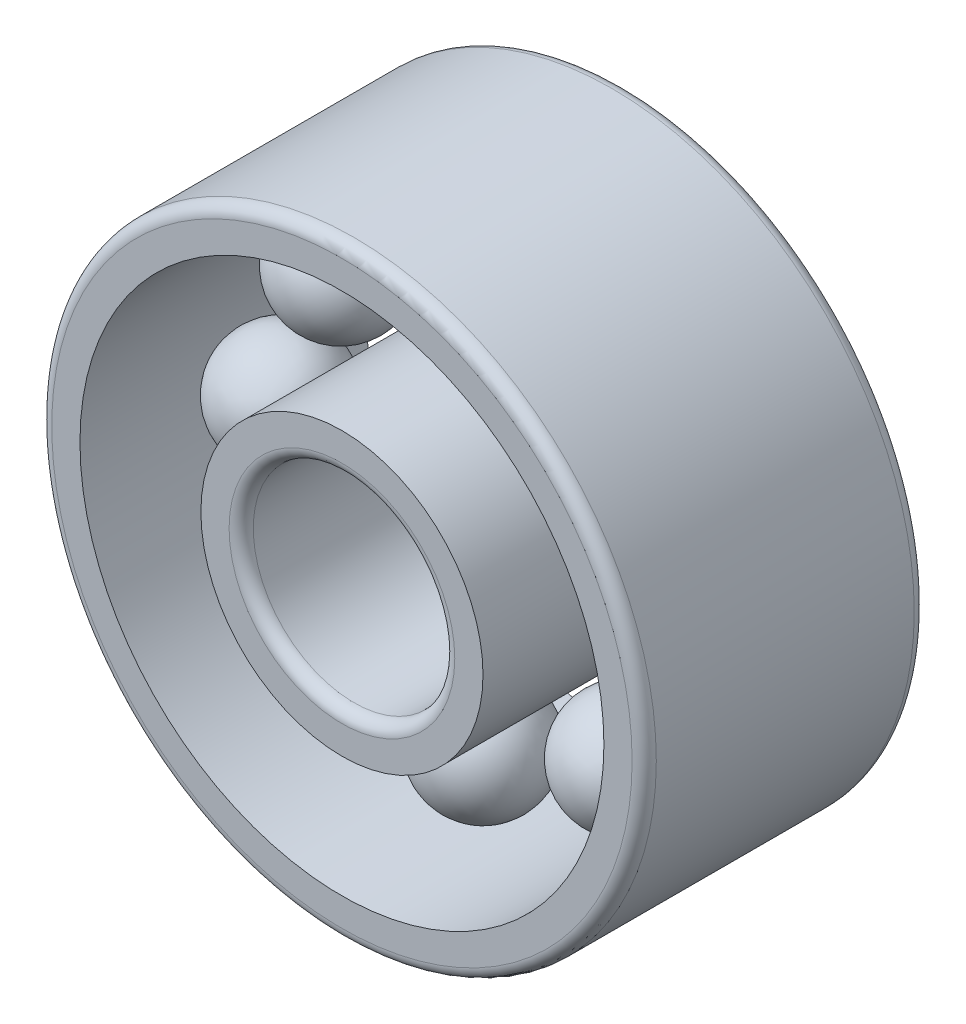
SolidWorks part; units mm, degrees
ref_plane "Front Plane" through (0, 0, 0) normal (0, 0, 1) x (1, 0, 0)
ref_plane "Top Plane" through (0, 0, 0) normal (0, 1, 0) x (1, 0, 0)
ref_plane "Right Plane" through (0, 0, 0) normal (1, 0, 0) x (0, 0, -1)
sketch "S" plane through (0, 0, 0) normal (0, 0, 1) x (1, 0, 0)
  line L0 (-7, 0) -> (7, 0) construction
  circle A0 centre (0, 0) radius 5 construction
  circle A1 centre (0, 0) radius 15 construction
  circle A2 centre (0, 0) radius 7 construction
  circle A3 centre (0, 0) radius 13 construction
  dimension "ID" = 10
  dimension "OD" = 30
  dimension "IDa" = 14
  dimension "ODa" = 26
  dimension "B" = 14
ref_axis "Z" through (0, 0, -7.7) along (0, 0, 1)
sketch "InnerS" plane through (0, 0, 0) normal (0, 1, 0) x (1, 0, 0)
  line L0 (5, -7) -> (7, -7)
  line L1 (7, -7) -> (7, 7)
  line L2 (7, 7) -> (5, 7)
  line L3 (5, 7) -> (5, -7)
  line L4 (0, -11.5) -> (0, 11.5) construction
  dimension "r1" = 5
  dimension "r2" = 7
  dimension "z1" = 7
  dimension "z2" = 7
revolve "InnerRing" add sketch "InnerS" angle 360 about L4
sketch "OuterS" plane through (0, 0, 0) normal (0, 1, 0) x (1, 0, 0)
  line L0 (13, -7) -> (15, -7)
  line L1 (15, -7) -> (15, 7)
  line L2 (15, 7) -> (13, 7)
  line L3 (13, 7) -> (13, -7)
  line L4 (0, -11.5) -> (0, 11.5) construction
  dimension "r1" = 13
  dimension "r2" = 15
  dimension "z1" = 7
  dimension "z2" = 7
revolve "OuterRing" add sketch "OuterS" angle 360 about L4
sketch "BallS" plane through (0, 0, 0) normal (0, 1, 0) x (1, 0, 0)
  line L0 (7.15, 0) -> (12.85, 0)
  arc A0 (7.15, 0) -> (12.85, 0) centre (10, 0) ccw
  dimension "r" = 2.85
  dimension "p" = 10
revolve "Ball" add sketch "BallS" angle 360 about L0
pattern_circular "BallsPattern" count 8 over 360 about axis through (0, 0, -7.7) along (0, 0, 1) of bodies 103
fillet "F1" radius 0.6 2 edges at (15, 0, -7) (15, 0, 7)
fillet "F2" radius 0.6 2 edges at (5, 0, -7) (5, 0, 7)
equation "\"r1@InnerS\" = abs(0.5*\"ID@S\")"
equation "\"r2@InnerS\" = abs(0.5*\"IDa@S\")"
equation "\"z1@InnerS\" = abs(-0.5*\"B@S\")"
equation "\"z2@InnerS\" = abs(0.5*\"B@S\")"
equation "\"r1@OuterS\" = abs(0.5*\"ODa@S\")"
equation "\"r2@OuterS\" = abs(0.5*\"OD@S\")"
equation "\"z1@OuterS\" = abs(-0.5*\"B@S\")"
equation "\"z2@OuterS\" = abs(0.5*\"B@S\")"
equation "\"r@BallS\" = abs(0.2375*\"ODa@S\"-0.2375*\"IDa@S\")"
equation "\"p@BallS\" = abs(0.25*\"IDa@S\"+0.25*\"ODa@S\")"
equation "\"N@BallsPattern\" = int(2.417*(0.25*\"IDa@S\"+0.25*\"ODa@S\")/(0.2375*\"ODa@S\"-0.2375*\"IDa@S\"))"
equation "\"r_min@F2\" = \"r_min@F1\""
